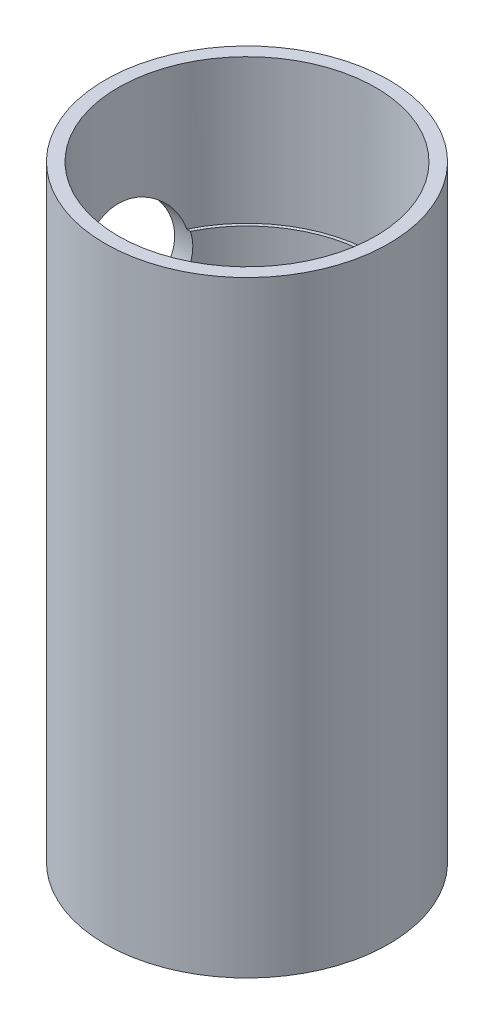
SolidWorks part; units mm, degrees
ref_plane "Front Plane" through (0, 0, 0) normal (0, 0, 1) x (1, 0, 0)
ref_plane "Top Plane" through (0, 0, 0) normal (0, 1, 0) x (1, 0, 0)
ref_plane "Right Plane" through (0, 0, 0) normal (1, 0, 0) x (0, 0, -1)
sketch "Sketch1" plane through (0, 0, 0) normal (0, 1, 0) x (1, 0, 0)
  line L0 (0, 38.25) -> (0, 43.25) construction
  circle A0 centre (0, 0) radius 38.25
  circle A1 centre (0, 0) radius 43.25
  dimension "D1" = 76.5
  dimension "D2" = 5
extrude "Boss-Extrude1" add sketch "Sketch1" along normal mid plane 185
sketch "Sketch2" plane through (0, -92.5, 0) normal (0, -1, 0) x (1, 0, 0)
  line L0 (0, 36.25) -> (0, 38.25) construction
  circle A0 centre (0, 0) radius 36.25
  circle A1 centre (0, 0) radius 38.25 construction
  circle A2 centre (0, 0) radius 38.25
  dimension "D1" = 2
extrude "Boss-Extrude2" add sketch "Sketch2" against normal blind 100 from offset 6.35 offset against normal yes
sketch "Sketch6" plane through (0, 92.5, 0) normal (0, 1, 0) x (1, 0, 0)
  line L0 (0, 38.25) -> (0, 39.25) construction
  circle A0 centre (0, 0) radius 39.25
  circle A1 centre (0, 0) radius 38.25 construction
  circle A2 centre (0, 0) radius 38.25
  dimension "D1" = 1
extrude "Cut-Extrude3" cut sketch "Sketch6" against normal blind 44
sketch "Sketch7" plane through (0, 0, 0) normal (1, 0, 0) x (0, 0, -1)
  line L0 (43.25, 92.5) -> (-43.25, 92.5) construction
  circle A0 centre (0, 44.35) radius 17.5
  point P4 (0, 0)
  point P6 (0, 0)
  dimension "D2" = 35
  dimension "D1" = 48.15
extrude "Cut-Extrude4" cut sketch "Sketch7" against normal through all
